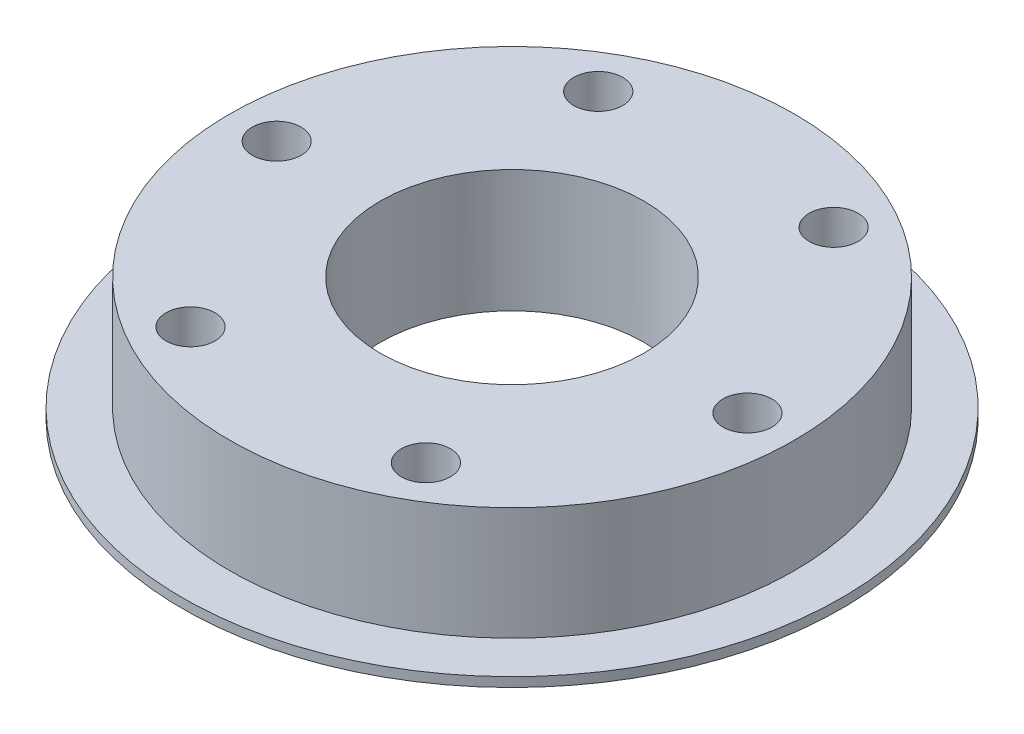
SolidWorks part; units mm, degrees
ref_plane "Front Plane" through (0, 0, 0) normal (0, 0, 1) x (1, 0, 0)
ref_plane "Top Plane" through (0, 0, 0) normal (0, 1, 0) x (1, 0, 0)
ref_plane "Right Plane" through (0, 0, 0) normal (1, 0, 0) x (0, 0, -1)
sketch "Sketch1" plane through (0, 0, 0) normal (0, 1, 0) x (1, 0, 0)
  circle A0 centre (0, 0) radius 30
  point P18 (0, 0)
  dimension "D4" = 60
extrude "Boss-Extrude1" add sketch "Sketch1" along normal blind 13
sketch "Sketch2" plane through (0, 0, 0) normal (0, -1, 0) x (1, 0, 0)
  circle A0 centre (0, 0) radius 35
  dimension "D1" = 70
extrude "Boss-Extrude2" add sketch "Sketch2" against normal blind 1
sketch "Sketch3" plane through (0, 0, 0) normal (0, 1, 0) x (1, 0, 0)
  circle A1 centre (0, 0) radius 25 construction
  circle A2 centre (0, 25) radius 1.75
  circle A3 centre (21.6506, 12.5) radius 1.75
  circle A4 centre (21.6506, -12.5) radius 1.75
  circle A5 centre (0, -25) radius 1.75
  circle A6 centre (-21.6506, -12.5) radius 1.75
  circle A7 centre (-21.6506, 12.5) radius 1.75
  point P30 (0, 0)
  dimension "D1" = 50
  dimension "D2" = 3.5
  dimension "D3" = 6
extrude "Cut-Extrude1" cut sketch "Sketch3" along normal blind 3.5
sketch "Sketch4" plane through (0, 0, 0) normal (0, -1, 0) x (1, 0, 0)
  circle A0 centre (0, 0) radius 14
  dimension "D1" = 28
extrude "Cut-Extrude2" cut sketch "Sketch4" against normal blind 51
sketch "Sketch5" plane through (0, 0, 0) normal (0, -1, 0) x (1, 0, 0)
  line L0 (-12.5, 21.6506) -> (0, 0) construction
  line L1 (0, 0) -> (0, 25) construction
  line L2 (0, 25) -> (-21.6506, 12.5) construction
  circle A0 centre (0, 0) radius 25 construction
  circle A1 centre (-12.5, 21.6506) radius 2.6
  circle A2 centre (12.5, 21.6506) radius 2.6
  circle A3 centre (25, 0) radius 2.6
  circle A4 centre (12.5, -21.6506) radius 2.6
  circle A5 centre (-12.5, -21.6506) radius 2.6
  circle A6 centre (-25, 0) radius 2.6
  point P21 (0, 0)
  dimension "D1" = 5.2
  dimension "D2" = 6
extrude "Cut-Extrude3" cut sketch "Sketch5" against normal blind 25
